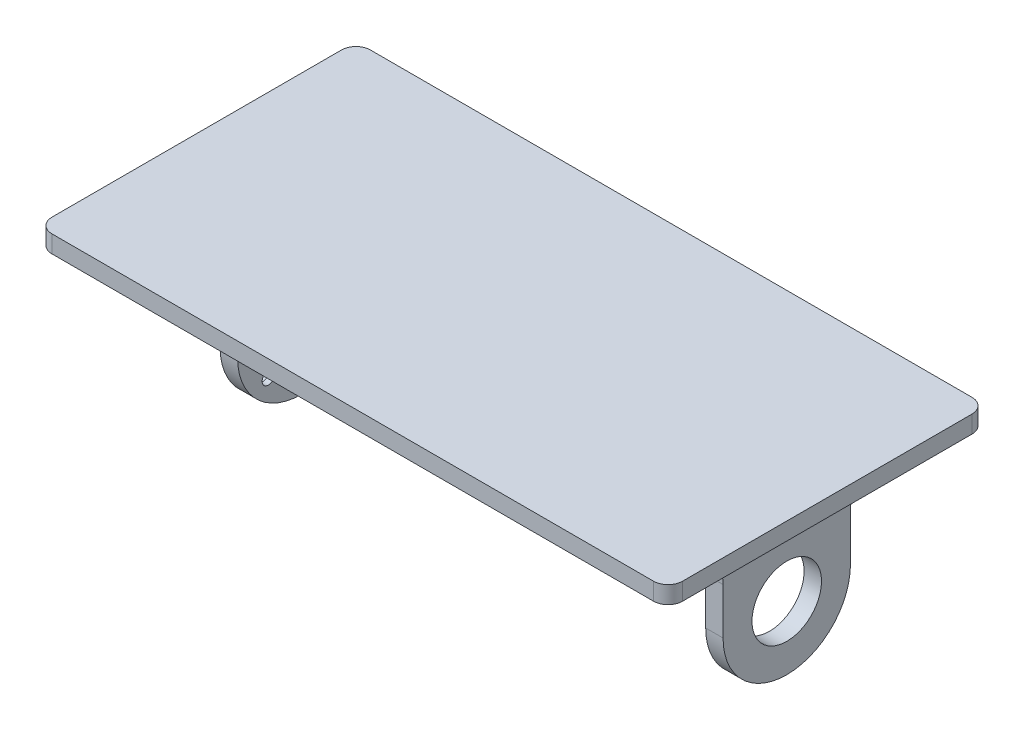
SolidWorks part; units mm, degrees
ref_plane "Front Plane" through (0, 0, 0) normal (0, 0, 1) x (1, 0, 0)
ref_plane "Top Plane" through (0, 0, 0) normal (0, 1, 0) x (1, 0, 0)
ref_plane "Right Plane" through (0, 0, 0) normal (1, 0, 0) x (0, 0, -1)
sketch "Sketch1" plane through (0, 0, 0) normal (0, 1, 0) x (1, 0, 0)
  line L5 (-40.425, 0) -> (40.425, 0) construction
  line L10 (-43.425, 11) -> (-43.425, -11)
  line L14 (43.425, 11) -> (43.425, -11)
  line L16 (-43.425, 11) -> (-40.425, 11)
  line L17 (-43.425, 11) -> (-43.425, -11)
  line L18 (-43.425, -11) -> (-40.425, -11)
  line L19 (-40.425, 11) -> (-40.425, -11)
  line L20 (43.425, 11) -> (40.425, 11)
  line L21 (43.425, 11) -> (43.425, -11)
  line L22 (43.425, -11) -> (40.425, -11)
  line L23 (40.425, 11) -> (40.425, -11)
  line L25 (-43.425, 11) -> (-43.425, -11)
  line L29 (43.425, 11) -> (43.425, -11)
  line L31 (50.425, 27.5) -> (50.425, -27.5)
  line L34 (50.425, 27.5) -> (-58.475, 27.5)
  line L35 (-58.475, -27.5) -> (-58.475, 27.5)
  line L37 (-58.475, -27.5) -> (50.425, -27.5)
  point P0 (-4.025, 0)
  point P1 (0, 0)
  point P3 (-43.425, 0)
  point P5 (0, 0)
  point P6 (-9.0665, 13.1407)
  point P7 (-58.475, -26.7203)
  point P11 (-14.2585, 12.159)
  point P12 (50.2615, -28.1209)
  point P15 (-4.025, -27.5)
  point P17 (50.425, 0)
  point P23 (0, 0)
  point P24 (0, 0)
  point P29 (-40.425, 0)
  point P30 (40.425, 0)
  dimension "D5" = 7
  dimension "D1" = 86.85
  dimension "D2" = 55
  dimension "D3" = 3
  dimension "D4" = 22
  dimension "D6" = 108.9
extrude "Boss-Extrude1" add sketch "Sketch1" along normal blind 3 contours L34 L35 L37 L31
sketch "Sketch5" plane through (0, 0, 0) normal (0, -1, 0) x (1, 0, 0)
  line L1 (-43.425, 11) -> (-40.425, 11)
  line L2 (-43.425, 11) -> (-43.425, -11)
  line L3 (-43.425, -11) -> (-40.425, -11)
  line L4 (-40.425, 11) -> (-40.425, -11)
  line L5 (40.425, 11) -> (43.425, 11)
  line L6 (40.425, 11) -> (40.425, -11)
  line L7 (40.425, -11) -> (43.425, -11)
  line L8 (43.425, 11) -> (43.425, -11)
  dimension "D2" = 3
extrude "Boss-Extrude2" add sketch "Sketch5" along normal blind 27
sketch "Sketch2" plane through (-43.425, 0, 0) normal (-1, 0, 0) x (0, 0, 1)
  line L0 (0, -16) -> (-5.6569, -21.6569) construction
  line L2 (11, -27) -> (-11, -27) construction
  circle A2 centre (0, -16) radius 3
  circle A3 centre (-5.6569, -21.6569) radius 1.1
  dimension "D1" = 8
  dimension "D5" = 11
  dimension "D2" = 6
  dimension "D3" = 2.2
  dimension "D4" = 45
extrude "Cut-Extrude1" cut sketch "Sketch2" against normal up to surface (3 mm away) contours A2 | A3 region at (-43.425, -16, 0) up to face at (-40.425, -13.5, 0)
pattern_circular "CirPattern1" count 4 over 360 about axis through (-43.425, -16, 0) along (-1, 0, 0) of "Cut-Extrude1"
fillet "Fillet3" radius 11 4 edges at (-41.925, -27, -11) (-41.925, -27, 11) (41.925, -27, -11) (41.925, -27, 11)
sketch "Sketch6" plane through (-43.425, 0, 0) normal (-1, 0, 0) x (0, 0, 1)
  circle A0 centre (5.6569, -10.3431) radius 2
  circle A1 centre (5.6569, -10.3431) radius 1.1 construction
  dimension "D1" = 4
extrude "Cut-Extrude5" cut sketch "Sketch6" against normal offset from surface (2 mm away) 1 up to face at (-40.425, -10.3431, -4.5569)
pattern_circular "CirPattern2" count 4 over 360 about axis through (-43.425, -16, 0) along (-1, 0, 0) of "Cut-Extrude5"
sketch "Sketch7" plane through (40.425, 0, 0) normal (-1, 0, 0) x (0, 0, 1)
  circle A1 centre (0, -16) radius 3 construction
  circle A2 centre (0, -16) radius 5
  circle A3 centre (0, -16) radius 6
  dimension "D2" = 12
  dimension "D3" = 1
extrude "Cut-Extrude6" cut sketch "Sketch7" against normal up to surface (10 mm away) contours A2 region at (40.425, -16, 0) up to face at (50.425, 1.5, 0)
extrude "Cut-Extrude7" cut sketch "Sketch7<5>" against normal offset from surface (9 mm away) 1 up to face at (50.425, 1.5, 0)
sketch "Sketch7<5>" plane through (40.425, 0, 0) normal (-1, 0, 0) x (0, 0, 1) same geometry as "Sketch7"
fillet "Fillet4" radius 8 7 edges at (-43.425, 0, 0) (40.425, 0, 0) (-40.425, 0, 0) (41.925, 0, 11) (41.925, 0, -11) (-41.925, 0, 11) (-41.925, 0, -11)
fillet "Filete1" radius 2.5 4 edges at (50.425, 1.5, 27.5) (50.425, 1.5, -27.5) (-58.475, 1.5, 27.5) (-58.475, 1.5, -27.5)
